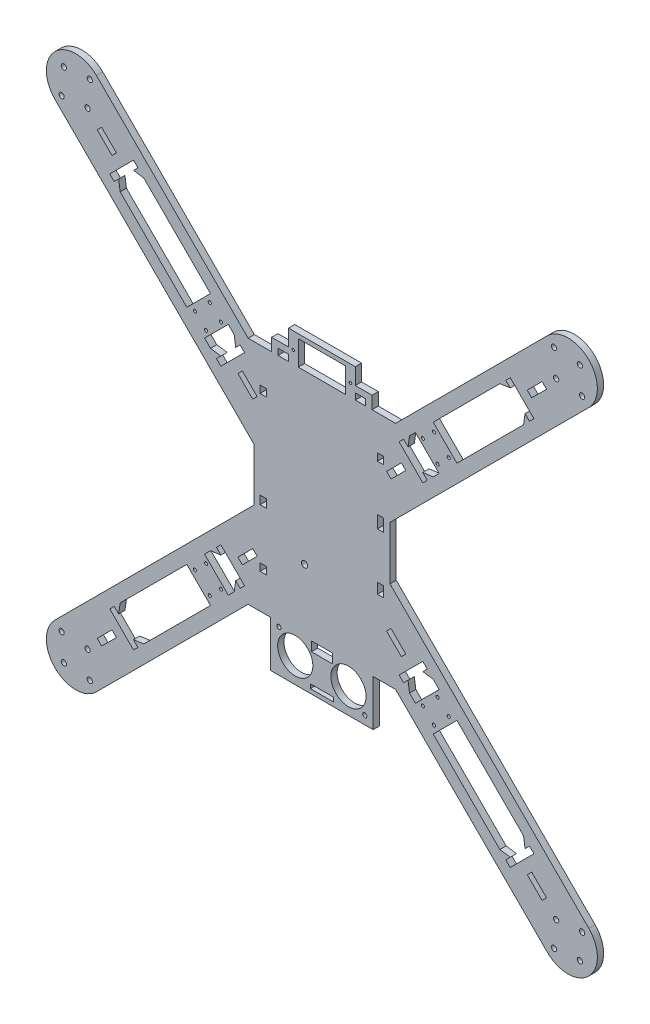
SolidWorks part; units mm, degrees
material "Custom Plastic"
ref_plane "Front Plane" through (0, 0, 0) normal (0, 0, 1) x (1, 0, 0)
ref_plane "Top Plane" through (0, 0, 0) normal (0, 1, 0) x (1, 0, 0)
ref_plane "Right Plane" through (0, 0, 0) normal (1, 0, 0) x (0, 0, -1)
sketch "Sketch1" plane through (0, 0, 0) normal (0, 0, 1) x (1, 0, 0)
  line L0 (117.5, 117.5) -> (-117.5, 117.5) construction
  line L1 (-117.5, 117.5) -> (117.5, -117.5) construction
  line L2 (117.5, -117.5) -> (-117.5, -117.5) construction
  line L3 (-117.5, -117.5) -> (117.5, 117.5) construction
  line L4 (117.5, 117.5) -> (117.5, -117.5) construction
  line L5 (-117.5, 117.5) -> (-117.5, -117.5) construction
  line L6 (0, 117.5) -> (0, -117.5) construction
  line L7 (35.201, 55) -> (15.95, 55)
  line L8 (-32.5, 55) -> (32.5, 55) construction
  line L9 (-35.201, 55) -> (-107.6005, 127.3995)
  line L10 (-127.3995, 107.6005) -> (-32.5, 12.701)
  line L11 (-117.5, 0) -> (117.5, 0) construction
  line L12 (-32.5, 12.701) -> (-32.5, -12.701)
  line L13 (32.5, 55) -> (32.5, -55) construction
  line L14 (32.5, -55) -> (-32.5, -55) construction
  line L15 (-32.5, -55) -> (-32.5, 55) construction
  line L16 (32.5, 55) -> (-32.5, -55) construction
  line L17 (-24.5, -55) -> (-24.5, -77)
  line L18 (-127.3995, -107.6005) -> (-32.5, -12.701)
  line L19 (-24.5, -77) -> (24.5, -77)
  line L20 (-35.201, -55) -> (-107.6005, -127.3995)
  line L21 (35.201, -55) -> (24.5, -55)
  line L22 (35.201, -55) -> (107.6005, -127.3995)
  line L23 (127.3995, -107.6005) -> (32.5, -12.701)
  line L24 (32.5, 12.701) -> (32.5, -12.701)
  line L25 (127.3995, 107.6005) -> (32.5, 12.701)
  line L26 (35.201, 55) -> (107.6005, 127.3995)
  line L27 (24.5, -55) -> (24.5, -77)
  line L28 (-24.5, -55) -> (-35.201, -55)
  line L29 (-15.95, 55) -> (-15.95, 68.8)
  line L30 (-15.95, 68.8) -> (15.95, 68.8)
  line L31 (15.95, 55) -> (15.95, 68.8)
  line L32 (-15.95, 55) -> (-35.201, 55)
  arc A0 (-107.6005, 127.3995) -> (-127.3995, 107.6005) centre (-117.5, 117.5) ccw
  arc A12 (-107.6005, -127.3995) -> (-127.3995, -107.6005) centre (-117.5, -117.5) cw
  arc A16 (107.6005, -127.3995) -> (127.3995, -107.6005) centre (117.5, -117.5) ccw
  arc A24 (107.6005, 127.3995) -> (127.3995, 107.6005) centre (117.5, 117.5) cw
  point P3 (0, 0)
  point P18 (0, 0)
  point P21 (0, -77)
  point P26 (0, 68.8)
  point P33 (-117.5, 117.5)
  point P34 (-32.5, 0)
  point P65 (0, -55)
  point P80 (0, 55)
  dimension "D3" = 14
  dimension "D8" = 24.5
  dimension "D7" = 22
  dimension "D1" = 235
  dimension "D2" = 235
  dimension "D4" = 65
  dimension "D5" = 110
  dimension "D6" = 28
  dimension "D9" = 13.8
  dimension "D10" = 31.9
extrude "Boss-Extrude1" add sketch "Sketch1" against normal blind 3
sketch "Sketch4" plane through (0, 0, 0) normal (0, 0, 1) x (1, 0, 0)
  line L0 (0, 0) -> (0, 55) construction
  line L2 (0, 0) -> (-32.5, 0) construction
  line L3 (-32.5, 12.701) -> (-32.5, -12.701) construction
  line L4 (-32.5, 0) -> (-32.5, 12.701) construction
  line L5 (-32.5, 12.701) -> (-127.3995, 107.6005) construction
  line L6 (-35.201, 55) -> (-107.6005, 127.3995) construction
  line L7 (-107.6005, 127.3995) -> (-127.3995, 107.6005) construction
  line L8 (-110.7825, 124.2175) -> (-124.2175, 110.7825) construction
  line L9 (-123.1569, 123.1569) -> (-111.8431, 111.8431) construction
  circle A20 centre (-110.7825, 124.2175) radius 1.25
  circle A21 centre (-124.2175, 110.7825) radius 1.25
  circle A22 centre (-123.1569, 123.1569) radius 1.25
  circle A23 centre (-111.8431, 111.8431) radius 1.25
  circle A24 centre (111.8431, 111.8431) radius 1.25
  circle A25 centre (110.7825, 124.2175) radius 1.25
  circle A26 centre (123.1569, 123.1569) radius 1.25
  circle A27 centre (124.2175, 110.7825) radius 1.25
  circle A28 centre (111.8431, -111.8431) radius 1.25
  circle A29 centre (124.2175, -110.7825) radius 1.25
  circle A30 centre (123.1569, -123.1569) radius 1.25
  circle A31 centre (110.7825, -124.2175) radius 1.25
  circle A32 centre (-111.8431, -111.8431) radius 1.25
  circle A33 centre (-110.7825, -124.2175) radius 1.25
  circle A34 centre (-123.1569, -123.1569) radius 1.25
  circle A35 centre (-124.2175, -110.7825) radius 1.25
  point P16 (-117.5, 117.5)
  point P19 (-117.5, 117.5)
  point P26 (-117.5, 117.5)
  point P62 (0, 0)
  dimension "D1" = 55
  dimension "D4" = 2.5
  dimension "D2" = 19
  dimension "D5" = 35.201
  dimension "D3" = 16
extrude "Cut-Extrude1" cut sketch "Sketch4" against normal blind 4.5
sketch "Sketch5" plane through (0, 0, 0) normal (0, 0, 1) x (1, 0, 0)
  line L4 (0, 0) -> (0, 14.0392) construction
  line L6 (15.95, 68.8) -> (-15.95, 68.8) construction
  line L7 (-11.25, 66.8) -> (-11.25, 55)
  line L8 (-11.25, 55) -> (11.25, 55)
  line L9 (11.25, 55) -> (11.25, 66.8)
  line L10 (11.25, 66.8) -> (-11.25, 66.8)
  line L12 (0, 66.8) -> (0, 55) construction
  line L13 (-13.65, 60.9) -> (13.65, 60.9) construction
  circle A2 centre (-13.65, 60.9) radius 0.65
  circle A3 centre (13.65, 60.9) radius 0.65
  point P20 (0, 60.9)
  point P21 (0, 60.9)
  dimension "D8" = 1.3
  dimension "D9" = 1.3
  dimension "D2" = 2
  dimension "D10" = 27.3
  dimension "D11" = 22.5
  dimension "D12" = 11.8
extrude "Cut-Extrude2" cut sketch "Sketch5" against normal blind 4.5
sketch "Sketch6" plane through (0, 0, 0) normal (0, 0, 1) x (1, 0, 0)
  line L1 (-11.25, 55) -> (11.25, 55) construction
  circle A0 centre (-8.25, -25) radius 1.5
  dimension "D3" = 3
  dimension "D1" = 80
  dimension "D2" = 3
extrude "Cut-Extrude3" cut sketch "Sketch6" against normal blind 4.5
sketch "Sketch7" plane through (0, 0, 0) normal (0, 0, 1) x (1, 0, 0)
  line L0 (-22.5, -55) -> (-22.5, -75) construction
  line L5 (-22.5, -75) -> (22.5, -75) construction
  line L6 (22.5, -75) -> (22.5, -55) construction
  line L7 (22.5, -55) -> (-22.5, -55) construction
  line L8 (0, -55) -> (0, -75) construction
  line L9 (-12.7, -65) -> (0, -65) construction
  line L10 (-24.5, -77) -> (24.5, -77) construction
  line L11 (-24.5, -55) -> (-24.5, -77) construction
  line L12 (-5, -55) -> (-5, -59.5)
  line L13 (-5, -59.5) -> (5, -59.5)
  line L15 (5, -55) -> (-5, -55)
  line L16 (-5.5, -75) -> (-5.5, -73)
  line L17 (-5.5, -73) -> (5.5, -73)
  line L21 (5.5, -75) -> (-5.5, -75)
  line L22 (5, -55) -> (5, -59.5)
  line L23 (5.5, -75) -> (5.5, -73)
  circle A5 centre (-20.5, -57) radius 1
  circle A6 centre (-12.7, -65) radius 8.4
  circle A7 centre (12.7, -65) radius 8.4
  circle A8 centre (20.5, -73) radius 1
  point P25 (0, -59.5)
  point P26 (0, -73)
  dimension "D3" = 2
  dimension "D6" = 20
  dimension "D13" = 5.5
  dimension "D5" = 45
  dimension "D1" = 2
  dimension "D4" = 16.8
  dimension "D14" = 2
  dimension "D2" = 2
  dimension "D7" = 2
  dimension "D8" = 2
  dimension "D9" = 12.7
  dimension "D10" = 5
  dimension "D11" = 4.5
  dimension "D12" = 2
  dimension "D15" = 2
  dimension "D16" = 2
extrude "Cut-Extrude4" cut sketch "Sketch7" against normal blind 4.5
sketch "Sketch8" plane through (0, 0, 0) normal (0, 0, 1) x (1, 0, 0)
  line L0 (101.2365, -89.9228) -> (89.9228, -101.2365)
  line L1 (89.9228, -101.2365) -> (87.8015, -99.1152)
  line L2 (36.8898, -48.2035) -> (48.2035, -36.8898)
  line L3 (48.2035, -36.8898) -> (50.3249, -39.0111)
  line L4 (105.4792, -85.6802) -> (85.6802, -105.4792) construction
  line L5 (127.3995, -107.6005) -> (32.5, -12.701) construction
  line L6 (35.201, -55) -> (107.6005, -127.3995) construction
  line L7 (40.0718, -37.9505) -> (37.9505, -40.0718)
  line L8 (115.8431, -107.8431) -> (111.8431, -111.8431) construction
  line L9 (37.9505, -40.0718) -> (30.8794, -33.0007)
  line L10 (50.3249, 39.0111) -> (48.2035, 36.8898)
  line L11 (30.8794, -33.0007) -> (33.0007, -30.8794)
  line L12 (33.0007, -30.8794) -> (40.0718, -37.9505)
  line L13 (42.5467, -42.5467) -> (39.0111, -39.0111) construction
  line L14 (35.201, -55) -> (107.6005, -127.3995) construction
  line L15 (100.1759, -98.0546) -> (98.0546, -100.1759)
  line L16 (98.0546, -100.1759) -> (105.1256, -107.247)
  line L17 (105.1256, -107.247) -> (107.247, -105.1256)
  line L18 (107.247, -105.1256) -> (100.1759, -98.0546)
  line L19 (99.1152, -99.1152) -> (95.5797, -95.5797) construction
  line L20 (-101.2365, -89.9228) -> (-99.1152, -87.8015)
  line L21 (-100.1759, -98.0546) -> (-107.247, -105.1256)
  line L22 (-107.247, -105.1256) -> (-105.1256, -107.247)
  line L23 (-105.1256, -107.247) -> (-98.0546, -100.1759)
  line L24 (-98.0546, -100.1759) -> (-100.1759, -98.0546)
  line L25 (-89.9228, -101.2365) -> (-101.2365, -89.9228)
  line L26 (-36.8898, -48.2035) -> (-39.0111, -50.3249)
  line L27 (-48.2035, -36.8898) -> (-36.8898, -48.2035)
  line L28 (-37.9505, -40.0718) -> (-40.0718, -37.9505)
  line L29 (-30.8794, -33.0007) -> (-37.9505, -40.0718)
  line L30 (-40.0718, -37.9505) -> (-33.0007, -30.8794)
  line L31 (-33.0007, -30.8794) -> (-30.8794, -33.0007)
  line L32 (-89.9228, 101.2365) -> (-87.8015, 99.1152)
  line L33 (-98.0546, 100.1759) -> (-105.1256, 107.247)
  line L34 (-105.1256, 107.247) -> (-107.247, 105.1256)
  line L35 (-107.247, 105.1256) -> (-100.1759, 98.0546)
  line L36 (-100.1759, 98.0546) -> (-98.0546, 100.1759)
  line L37 (-101.2365, 89.9228) -> (-89.9228, 101.2365)
  line L38 (-48.2035, 36.8898) -> (-50.3249, 39.0111)
  line L39 (-36.8898, 48.2035) -> (-48.2035, 36.8898)
  line L40 (-40.0718, 37.9505) -> (-37.9505, 40.0718)
  line L41 (-33.0007, 30.8794) -> (-40.0718, 37.9505)
  line L42 (-37.9505, 40.0718) -> (-30.8794, 33.0007)
  line L43 (-30.8794, 33.0007) -> (-33.0007, 30.8794)
  line L44 (101.2365, 89.9228) -> (99.1152, 87.8015)
  line L45 (100.1759, 98.0546) -> (107.247, 105.1256)
  line L46 (107.247, 105.1256) -> (105.1256, 107.247)
  line L47 (105.1256, 107.247) -> (98.0546, 100.1759)
  line L48 (98.0546, 100.1759) -> (100.1759, 98.0546)
  line L49 (89.9228, 101.2365) -> (101.2365, 89.9228)
  line L50 (36.8898, 48.2035) -> (39.0111, 50.3249)
  line L51 (48.2035, 36.8898) -> (36.8898, 48.2035)
  line L52 (37.9505, 40.0718) -> (40.0718, 37.9505)
  line L53 (30.8794, 33.0007) -> (37.9505, 40.0718)
  line L54 (40.0718, 37.9505) -> (33.0007, 30.8794)
  line L55 (33.0007, 30.8794) -> (30.8794, 33.0007)
  line L56 (32.5, 12.701) -> (127.3995, 107.6005) construction
  line L57 (41.8396, 53.1533) -> (84.9731, 96.2868)
  line L58 (96.2868, 84.9731) -> (53.1533, 41.8396)
  line L59 (87.8015, 99.1152) -> (89.9228, 101.2365)
  line L60 (99.1152, -87.8015) -> (96.9939, -89.9228)
  line L61 (-96.2868, -84.9731) -> (-53.1533, -41.8396)
  line L62 (96.9939, -89.9228) -> (96.2868, -84.9731)
  line L63 (99.1152, -87.8015) -> (101.2365, -89.9228)
  line L64 (87.8015, -99.1152) -> (89.9228, -96.9939)
  line L65 (-87.8015, -99.1152) -> (-89.9228, -101.2365)
  line L66 (89.9228, -96.9939) -> (84.9731, -96.2868)
  line L67 (84.9731, -96.2868) -> (41.8396, -53.1533)
  line L68 (50.3249, -39.0111) -> (48.2035, -41.1325)
  line L69 (48.2035, -41.1325) -> (53.1533, -41.8396)
  line L70 (53.1533, -41.8396) -> (96.2868, -84.9731)
  line L71 (39.0111, -50.3249) -> (41.1325, -48.2035)
  line L72 (41.1325, -48.2035) -> (41.8396, -53.1533)
  line L73 (39.0111, -50.3249) -> (36.8898, -48.2035)
  line L74 (-89.9228, -96.9939) -> (-84.9731, -96.2868)
  line L75 (-87.8015, -99.1152) -> (-89.9228, -96.9939)
  line L76 (-96.9939, -89.9228) -> (-96.2868, -84.9731)
  line L77 (-99.1152, -87.8015) -> (-96.9939, -89.9228)
  line L78 (-41.1325, -48.2035) -> (-41.8396, -53.1533)
  line L79 (-39.0111, -50.3249) -> (-41.1325, -48.2035)
  line L80 (-48.2035, -41.1325) -> (-53.1533, -41.8396)
  line L81 (-50.3249, -39.0111) -> (-48.2035, -41.1325)
  line L82 (-96.9939, 89.9228) -> (-96.2868, 84.9731)
  line L83 (-99.1152, 87.8015) -> (-96.9939, 89.9228)
  line L84 (-89.9228, 96.9939) -> (-84.9731, 96.2868)
  line L85 (-87.8015, 99.1152) -> (-89.9228, 96.9939)
  line L86 (-48.2035, 41.1325) -> (-53.1533, 41.8396)
  line L87 (-50.3249, 39.0111) -> (-48.2035, 41.1325)
  line L88 (-41.1325, 48.2035) -> (-41.8396, 53.1533)
  line L89 (-39.0111, 50.3249) -> (-41.1325, 48.2035)
  line L90 (89.9228, 96.9939) -> (84.9731, 96.2868)
  line L91 (87.8015, 99.1152) -> (89.9228, 96.9939)
  line L92 (96.9939, 89.9228) -> (96.2868, 84.9731)
  line L93 (99.1152, 87.8015) -> (96.9939, 89.9228)
  line L94 (41.1325, 48.2035) -> (41.8396, 53.1533)
  line L95 (39.0111, 50.3249) -> (41.1325, 48.2035)
  line L96 (48.1429, 41.1931) -> (53.1533, 41.8396)
  line L97 (50.3249, 39.0111) -> (48.1429, 41.1931)
  line L98 (-39.0111, 50.3249) -> (-36.8898, 48.2035)
  line L99 (-53.1533, 41.8396) -> (-96.2868, 84.9731)
  line L100 (-99.1152, 87.8015) -> (-101.2365, 89.9228)
  line L101 (-84.9731, 96.2868) -> (-41.8396, 53.1533)
  line L102 (-41.8396, -53.1533) -> (-84.9731, -96.2868)
  line L103 (-50.3249, -39.0111) -> (-48.2035, -36.8898)
  line L104 (96.2868, 84.9731) -> (84.9731, 96.2868) construction
  line L105 (53.1533, 41.8396) -> (41.8396, 53.1533) construction
  point P10 (95.5797, -95.5797)
  point P11 (95.5797, -95.5797)
  point P18 (-49.2642, 40.0718)
  point P19 (-49.2642, -40.0718)
  point P68 (0, 0)
  point P122 (0, 0)
  dimension "D1" = 23
  dimension "D2" = 75
  dimension "D3" = 3
  dimension "D4" = 10
  dimension "D5" = 5
  dimension "D6" = 6
  dimension "D7" = 3
  dimension "D8" = 10
  dimension "D9" = 5
  dimension "D11" = 6
  dimension "D12" = 3
  dimension "D13" = 4
  dimension "D14" = 3
  dimension "D15" = 3
  dimension "D16" = 4
  dimension "D17" = 3
  dimension "D18" = 3
  dimension "D19" = 4
  dimension "D20" = 3
  dimension "D21" = 3
  dimension "D22" = 4
  dimension "D23" = 3
  dimension "D24" = 3
  dimension "D25" = 4
  dimension "D26" = 3
  dimension "D27" = 4
  dimension "D28" = 3
  dimension "D29" = 3
  dimension "D30" = 4
  dimension "D31" = 4
  dimension "D32" = 3
  dimension "D33" = 3
  dimension "D34" = 4
  dimension "D35" = 4
  dimension "D36" = 3
  dimension "D37" = 3
  dimension "D38" = 4
  dimension "D39" = 4
  dimension "D40" = 3
  dimension "D41" = 3
  dimension "D42" = 4
  dimension "D43" = 4
  dimension "D10" = 4
extrude "Cut-Extrude5" cut sketch "Sketch8" against normal through all
sketch "Sketch9" plane through (-5.6569, 5.6569, 0) normal (0.7071, -0.7071, 0) x (0, 0, -1)
  line L0 (3, 128.1701) -> (3, 67.1701) construction
  line L1 (3, 83.1701) -> (0, 83.1701)
  line L2 (3, 83.1701) -> (3, 71.1701)
  line L3 (3, 71.1701) -> (0, 71.1701)
  line L4 (0, 83.1701) -> (0, 71.1701)
  line L5 (0, 128.1701) -> (0, 67.1701) construction
  line L6 (0, 0) -> (28.0274, 0) construction
  line L7 (3, 63.1701) -> (0, 63.1701) construction
  dimension "D1" = 8
  dimension "D2" = 12
extrude "Boss-Extrude2" add sketch "Sketch9" along normal up to next
sketch "Sketch11" plane through (5.6569, 5.6569, 0) normal (-0.7071, -0.7071, 0) x (0, 0, 1)
  line L0 (-3, -128.1701) -> (-3, -67.1701) construction
  line L1 (-3, -71.1701) -> (0, -71.1701)
  line L2 (-3, -71.1701) -> (-3, -83.1701)
  line L3 (-3, -83.1701) -> (0, -83.1701)
  line L4 (0, -71.1701) -> (0, -83.1701)
  line L5 (0, -128.1701) -> (0, -67.1701) construction
  line L6 (-3, -63.1701) -> (0, -63.1701) construction
  dimension "D1" = 8
  dimension "D2" = 12
extrude "Boss-Extrude3" add sketch "Sketch11" along normal up to next
sketch "Sketch12" plane through (5.6569, -5.6569, 0) normal (-0.7071, 0.7071, 0) x (0, 0, 1)
  line L0 (-3, -128.1701) -> (-3, -67.1701) construction
  line L1 (-3, -71.1701) -> (0, -71.1701)
  line L2 (-3, -71.1701) -> (-3, -83.1701)
  line L3 (-3, -83.1701) -> (0, -83.1701)
  line L4 (0, -71.1701) -> (0, -83.1701)
  line L5 (0, -128.1701) -> (0, -67.1701) construction
  dimension "D1" = 8
  dimension "D2" = 12
extrude "Boss-Extrude4" add sketch "Sketch12" along normal up to next
sketch "Sketch13" plane through (5.6569, 5.6569, 0) normal (-0.7071, -0.7071, 0) x (0, 0, 1)
  line L0 (-3, 67.1701) -> (-3, 128.1701) construction
  line L1 (-3, 71.1701) -> (0, 71.1701)
  line L2 (-3, 71.1701) -> (-3, 83.1701)
  line L3 (-3, 83.1701) -> (0, 83.1701)
  line L4 (0, 71.1701) -> (0, 83.1701)
  line L5 (0, 67.1701) -> (0, 128.1701) construction
  dimension "D1" = 8
  dimension "D2" = 12
extrude "Boss-Extrude5" add sketch "Sketch13" along normal up to next
sketch "Sketch14" plane through (0, 0, -3) normal (0, 0, -1) x (-1, 0, 0)
  line L0 (32.5, 0) -> (-32.5, 0) construction
  line L1 (32.5, 12.701) -> (32.5, -12.701) construction
  line L2 (-32.5, -12.701) -> (-32.5, 12.701) construction
  line L3 (28, -38.5) -> (28, 38.5) construction
  line L14 (-26.5, 13) -> (-26.5, 7)
  line L17 (-26.5, 7) -> (-29.5, 7)
  line L19 (-26.5, 13) -> (-29.5, 13)
  line L23 (26.5, -38.5) -> (29.5, -38.5)
  line L24 (26.5, -38.5) -> (26.5, -35)
  line L25 (26.5, -35) -> (29.5, -35)
  line L26 (29.5, -38.5) -> (29.5, -35)
  line L27 (26.5, -11) -> (29.5, -11)
  line L28 (26.5, -11) -> (26.5, -7)
  line L29 (26.5, -7) -> (29.5, -7)
  line L30 (29.5, -11) -> (29.5, -7)
  line L31 (26.5, 35) -> (29.5, 35)
  line L32 (26.5, 35) -> (26.5, 38.5)
  line L33 (26.5, 38.5) -> (29.5, 38.5)
  line L34 (29.5, 35) -> (29.5, 38.5)
  line L35 (-29.5, 13) -> (-29.5, 7)
  line L36 (32.5, 12.701) -> (32.5, -12.701) construction
  line L37 (-26.5, -20) -> (-29.5, -20)
  line L38 (-26.5, -20) -> (-26.5, -15)
  line L39 (-26.5, -15) -> (-29.5, -15)
  line L40 (-29.5, -20) -> (-29.5, -15)
  line L41 (-26.5, 35) -> (-29.5, 35)
  line L42 (-26.5, 35) -> (-26.5, 38.5)
  line L43 (-26.5, 38.5) -> (-29.5, 38.5)
  line L44 (-29.5, 35) -> (-29.5, 38.5)
  line L45 (-32.5, -12.701) -> (-32.5, 12.701) construction
  point P11 (28, -38.5)
  point P16 (28, 0)
  point P28 (-28, 13)
  point P38 (-28, 7)
  dimension "D2" = 3
  dimension "D3" = 3.5
  dimension "D4" = 24
  dimension "D5" = 7
  dimension "D6" = 22
  dimension "D7" = 6
  dimension "D8" = 3.5
  dimension "D9" = 22
  dimension "D10" = 4
  dimension "D11" = 3.5
  dimension "D12" = 42
  dimension "D13" = 5
  dimension "D14" = 3
  dimension "D15" = 3
  dimension "D16" = 3
  dimension "D17" = 7
extrude "Cut-Extrude6" cut sketch "Sketch14" against normal through all
sketch "Sketch15" plane through (0, 0, -3) normal (0, 0, -1) x (-1, 0, 0)
  line L0 (-55.2746, -48.2035) -> (-48.2035, -55.2746) construction
  line L1 (-48.2035, -55.2746) -> (-53.5068, -60.5779) construction
  line L2 (-53.5068, -60.5779) -> (-60.5779, -53.5068) construction
  line L3 (-60.5779, -53.5068) -> (-55.2746, -48.2035) construction
  line L4 (-64.2902, -44.4912) -> (-44.4912, -64.2902) construction
  line L5 (-127.3995, -107.6005) -> (-32.5, -12.701) construction
  line L6 (-35.201, -55) -> (-107.6005, -127.3995) construction
  line L7 (-57.0424, -57.0424) -> (-51.7391, -51.7391) construction
  line L8 (-53.1533, -64.467) -> (-64.467, -53.1533) construction
  circle A6 centre (-60.5779, -53.5068) radius 0.75
  circle A7 centre (-55.2746, -48.2035) radius 0.75
  circle A8 centre (-48.2035, -55.2746) radius 0.75
  circle A9 centre (-53.5068, -60.5779) radius 0.75
  circle A10 centre (-53.5068, 60.5779) radius 0.75
  circle A11 centre (-48.2035, 55.2746) radius 0.75
  circle A12 centre (-60.5779, 53.5068) radius 0.75
  circle A13 centre (-55.2746, 48.2035) radius 0.75
  circle A14 centre (60.5779, 53.5068) radius 0.75
  circle A15 centre (55.2746, 48.2035) radius 0.75
  circle A16 centre (53.5068, 60.5779) radius 0.75
  circle A17 centre (48.2035, 55.2746) radius 0.75
  circle A18 centre (53.5068, -60.5779) radius 0.75
  circle A19 centre (48.2035, -55.2746) radius 0.75
  circle A20 centre (60.5779, -53.5068) radius 0.75
  circle A21 centre (55.2746, -48.2035) radius 0.75
  point P12 (-54.3907, -54.3907)
  point P19 (-54.3907, -54.3907)
  point P47 (0, 0)
  dimension "D3" = 1.5
  dimension "D1" = 7.5
  dimension "D2" = 10
  dimension "D4" = 2.5
  dimension "D5" = 4
extrude "Cut-Extrude7" cut sketch "Sketch15" against normal through all
sketch "Sketch17" plane through (0, 0, -3) normal (0, 0, -1) x (-1, 0, 0)
  line L0 (0, 68.8) -> (0, 41.1241) construction
  line L1 (15.95, 55) -> (23.95, 55)
  line L2 (15.95, 55) -> (15.95, 61)
  line L3 (15.95, 61) -> (23.95, 61)
  line L4 (23.95, 55) -> (23.95, 61)
  line L5 (-15.95, 68.8) -> (15.95, 68.8) construction
  line L6 (-15.95, 55) -> (-15.95, 58)
  line L7 (20.95, 55) -> (15.95, 55)
  line L10 (15.95, 55) -> (15.95, 58)
  line L11 (-20.95, 58) -> (-15.95, 58)
  line L12 (-20.95, 55) -> (-20.95, 58)
  line L13 (-20.95, 55) -> (-15.95, 55)
  line L14 (-23.95, 55) -> (-23.95, 61)
  line L15 (-15.95, 61) -> (-23.95, 61)
  line L16 (-15.95, 55) -> (-15.95, 61)
  line L17 (-15.95, 55) -> (-23.95, 55)
  point P12 (0, 0)
  dimension "D1" = 6
  dimension "D2" = 8
extrude "Boss-Extrude8" add sketch "Sketch17" against normal blind 3 contours L2 L3 L4 L1 | L16 L15 L14 L17
sketch "Sketch19" plane through (0, 0, -3) normal (0, 0, -1) x (-1, 0, 0)
  line L0 (15.95, 61) -> (23.95, 61) construction
  line L1 (20.95, 58) -> (15.95, 58)
  line L2 (20.95, 58) -> (20.95, 55)
  line L3 (20.95, 55) -> (15.95, 55)
  line L4 (15.95, 58) -> (15.95, 55)
  line L5 (23.95, 55) -> (23.95, 61) construction
  line L6 (0, 68.8) -> (0, 43.8944) construction
  line L7 (-15.95, 68.8) -> (15.95, 68.8) construction
  line L8 (-15.95, 58) -> (-15.95, 55)
  line L9 (-20.95, 55) -> (-15.95, 55)
  line L10 (-20.95, 58) -> (-20.95, 55)
  line L11 (-20.95, 58) -> (-15.95, 58)
  dimension "D1" = 5
  dimension "D2" = 3
  dimension "D3" = 3
  dimension "D4" = 3
extrude "Cut-Extrude9" cut sketch "Sketch19" against normal through all
